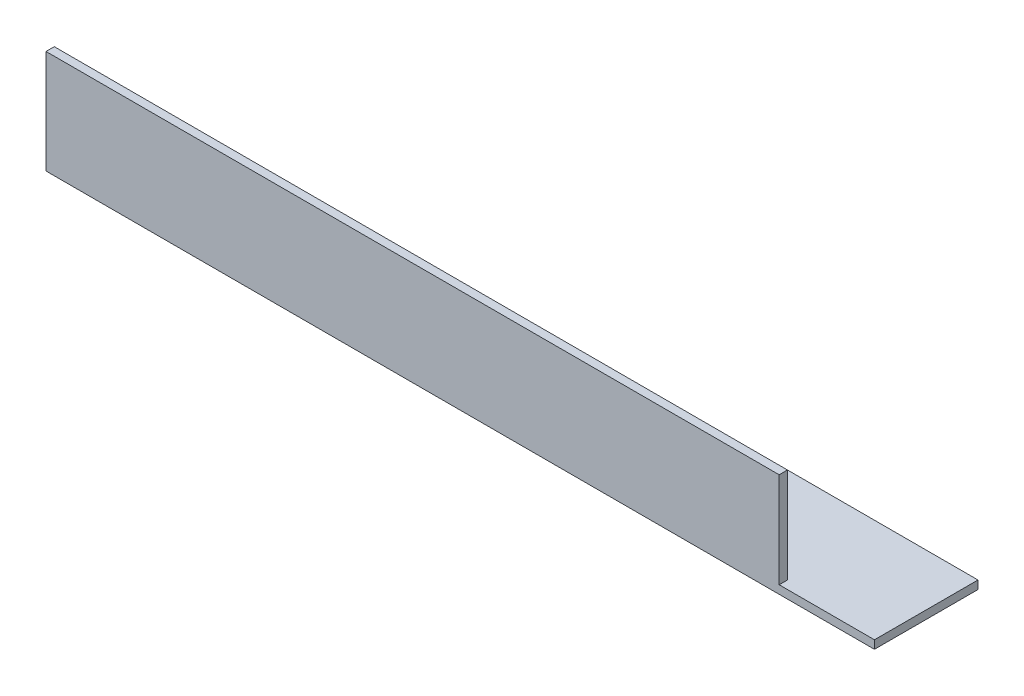
SolidWorks part; units mm, degrees
ref_plane "Спереди" through (0, 0, 0) normal (0, 0, 1) x (1, 0, 0)
ref_plane "Сверху" through (0, 0, 0) normal (0, 1, 0) x (1, 0, 0)
ref_plane "Справа" through (0, 0, 0) normal (1, 0, 0) x (0, 0, -1)
sketch "Эскиз1" plane through (0, 0, 0) normal (1, 0, 0) x (0, 0, -1)
  line L0 (0, 25) -> (0, 0)
  line L1 (0, 0) -> (25, 0)
extrude "Вытянуть-Тонкостенный1" add sketch "Эскиз1" along normal blind 200 thin thin type one direction reverse wall 2
sketch "Эскиз3" plane through (0, 0, 0) normal (0, 0, 1) x (1, 0, 0)
  line L1 (177, 2) -> (200, 2)
  line L2 (177, 2) -> (177, 25)
  line L3 (177, 25) -> (200, 25)
  line L4 (200, 2) -> (200, 25)
  dimension "D1" = 23
extrude "Вырез-Вытянуть1" cut sketch "Эскиз3" against normal through all
